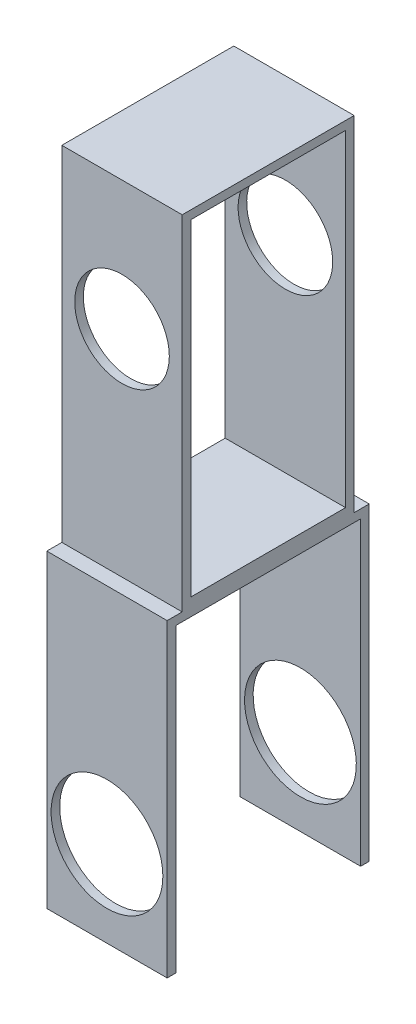
SolidWorks part; units mm, degrees
ref_plane "Front Plane" through (0, 0, 0) normal (0, 0, 1) x (1, 0, 0)
ref_plane "Top Plane" through (0, 0, 0) normal (0, 1, 0) x (1, 0, 0)
ref_plane "Right Plane" through (0, 0, 0) normal (1, 0, 0) x (0, 0, -1)
sketch "Sketch1" plane through (0, 0, 0) normal (0, 0, 1) x (1, 0, 0)
  line L1 (-14, 76) -> (14, 76)
  line L2 (-14, 76) -> (-14, -76)
  line L3 (-14, -76) -> (14, -76)
  line L4 (14, 76) -> (14, -76)
  line L5 (-14, 76) -> (14, -76) construction
  line L6 (-14, -76) -> (14, 76) construction
  line L8 (14, -4) -> (-14, -4)
  circle A0 centre (0, 46) radius 11
  circle A1 centre (0, -56) radius 13
  point P0 (0, 0)
  point P6 (-14, 46)
  point P7 (-14, -56)
  point P12 (14, -4)
  dimension "D4" = 80
  dimension "D6" = 22
  dimension "D1" = 28
  dimension "D2" = 152
  dimension "D3" = 30
  dimension "D5" = 20
extrude "Boss-Extrude1" add sketch "Sketch1" along normal blind 40 contours L8 L4 L1 L2 A0 region at (0, 33.9561, 0)
extrude "Boss-Extrude2" add sketch "Sketch1<4>" along normal blind 43.5 contours L4 L8 L2 L3 A1 region at (0, -34.2798, 0)
sketch "Sketch1<4>" plane through (0, 0, 0) normal (0, 0, 1) x (1, 0, 0) same geometry as "Sketch1"
extrude "Boss-Extrude3" add sketch "Sketch1<5>" against normal blind 3.5 contours L4 L8 L2 L3 A1 region at (0, -34.2798, 0)
sketch "Sketch1<5>" plane through (0, 0, 0) normal (0, 0, 1) x (1, 0, 0) same geometry as "Sketch1"
sketch "Sketch3" plane through (14, 0, 0) normal (1, 0, 0) x (0, 0, -1)
  line L0 (-40, -4) -> (0, -4)
  line L1 (-20, -4) -> (-20, 76)
  line L2 (-40, 76) -> (0, 76) construction
  line L3 (-20, -4) -> (-20, -76)
  line L4 (-43.5, -76) -> (3.5, -76) construction
  line L6 (-38, 74) -> (-2, 74)
  line L7 (-38, 74) -> (-38, -2)
  line L8 (-38, -2) -> (-2, -2)
  line L9 (-2, 74) -> (-2, -2)
  line L10 (-38, 74) -> (-2, -2) construction
  line L11 (-38, -2) -> (-2, 74) construction
  line L12 (-41.5, -6) -> (1.5, -6)
  line L13 (-41.5, -6) -> (-41.5, -76)
  line L14 (-41.5, -76) -> (1.5, -76)
  line L15 (1.5, -6) -> (1.5, -76)
  point P8 (-20, 36)
  point P16 (-20, -40)
  point P25 (-41.5, -6)
  line M14 (-43.5, -76) -> (3.5, -76)
  dimension "D1" = 36
  dimension "D2" = 76
  dimension "D3" = 43
extrude "Cut-Extrude1" cut sketch "Sketch3" against normal blind 28 contours L7 L8 L1 L6 | L9 L6 L1 L8 region at (14, 36, 29) region at (14, 36, 11)
extrude "Cut-Extrude2" cut sketch "Sketch3<4>" against normal blind 28 contours L15 L12 L3 M14 | L12 L13 L3 M14 region at (14, -41, 9.25) region at (14, -41, 30.75)
sketch "Sketch3<4>" plane through (14, 0, 0) normal (1, 0, 0) x (0, 0, -1) same geometry as "Sketch3"
sketch "Sketch4" plane through (0, 0, 0) normal (1, 0, 0) x (0, 0, -1)
  line L3 (-43.5, -56.4324) -> (-43.5, -55.8)
  line L4 (-43.5, -55.8) -> (3.5, -55.8)
  point P0 (-20, -55.8)
ref_point "Point4"
ref_point "Point5"
ref_point "Point6"
ref_plane "Plane1" through (0, 46, 0) normal (0, 1, 0) x (1, 0, 0)
sketch "Sketch5" plane through (0, 46, 0) normal (0, 1, 0) x (1, 0, 0)
  line L0 (0, -2) -> (0, -40)
  point P4 (0, -21)
